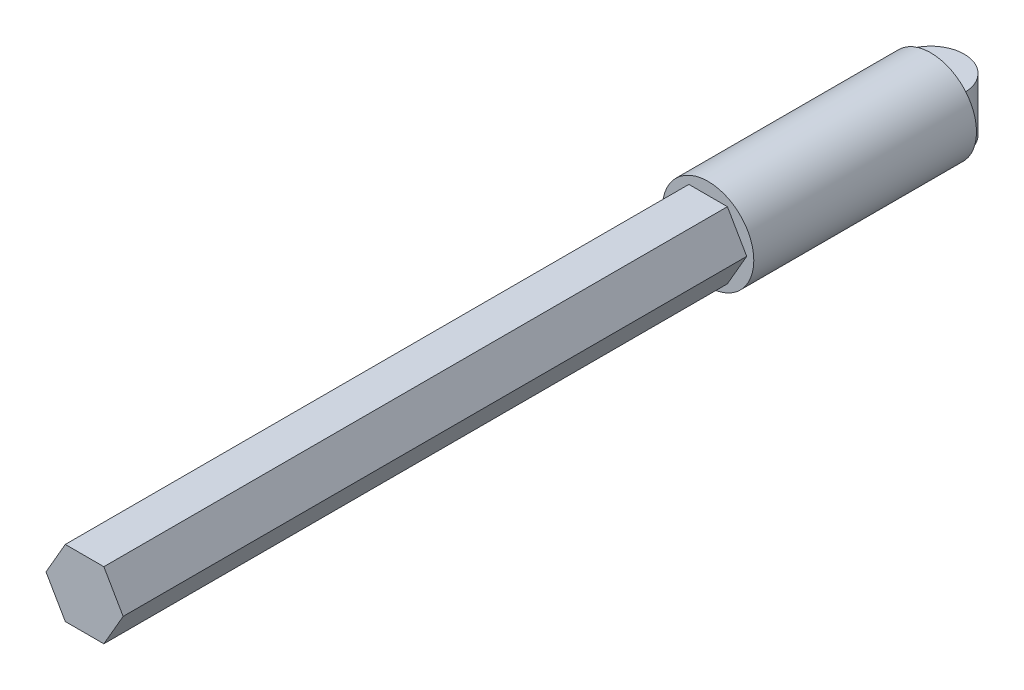
SolidWorks part; units mm, degrees
ref_plane "Front Plane" through (0, 0, 0) normal (0, 0, 1) x (1, 0, 0)
ref_plane "Top Plane" through (0, 0, 0) normal (0, 1, 0) x (1, 0, 0)
ref_plane "Right Plane" through (0, 0, 0) normal (1, 0, 0) x (0, 0, -1)
sketch "Sketch1" plane through (0, 0, 0) normal (0, 0, 1) x (1, 0, 0)
  circle A0 centre (0, 0) radius 1.025
  dimension "D1" = 2.05
extrude "Boss-Extrude1" add sketch "Sketch1" along normal blind 5
sketch "Sketch2" plane through (0, 0, 5) normal (0, 0, 1) x (1, 0, 0)
  line L0 (0, 0) -> (1.025, 0)
  line L2 (0.866, 0) -> (0.433, 0.75)
  line L3 (0.433, 0.75) -> (-0.433, 0.75)
  line L4 (-0.433, 0.75) -> (-0.866, 0)
  line L5 (-0.866, 0) -> (-0.433, -0.75)
  line L6 (-0.433, -0.75) -> (0.433, -0.75)
  line L7 (0.433, -0.75) -> (0.866, 0)
  circle A0 centre (0, 0) radius 1.025 construction
  circle A1 centre (0, 0) radius 0.75 construction
  dimension "D1" = 0.866
extrude "Boss-Extrude4" add sketch "Sketch2" along normal blind 14 contours L2 L3 L4 L5 L6 L7
ref_plane "Plane3" through (0, 0, 0) normal (0, 1, 0) x (1, 0, 0)
sketch "Sketch3" plane through (0, 0, 0) normal (0, 1, 0) x (1, 0, 0)
  line L0 (-0.75, 0) -> (0.75, 0)
  arc A0 (0.75, 0) -> (-0.75, 0) centre (0, 0) ccw
  dimension "D1" = 1.5
extrude "Boss-Extrude5" add sketch "Sketch3" along normal blind 0.25 and the other way blind 0.2 contours A0 L0
sketch "Sketch5" plane through (0, 0.25, 0) normal (0, 1, 0) x (1, 0, 0)
  line L0 (-0.75, 0) -> (0.75, 0)
  circle A0 centre (0, 0) radius 0.75
  arc M1 (0.75, 0) -> (-0.75, 0) centre (0, 0) ccw
  line M2 (-0.75, 0) -> (0.75, 0)
  dimension "D1" = 1.5
extrude "Boss-Extrude6" add sketch "Sketch5" along normal blind 0.375 contours M2 M1 region at (0, 0.25, -0.3183)
sketch "Sketch6" plane through (0, -0.2, 0) normal (0, -1, 0) x (1, 0, 0)
  line L0 (-0.75, 0) -> (0.75, 0)
  circle A0 centre (0, 0) radius 0.75
  arc M2 (-0.75, 0) -> (0.75, 0) centre (0, 0) ccw
  line M3 (0.75, 0) -> (-0.75, 0)
extrude "Boss-Extrude7" add sketch "Sketch6" along normal blind 0.375 contours M3 M2 region at (0, -0.2, -0.3183)
